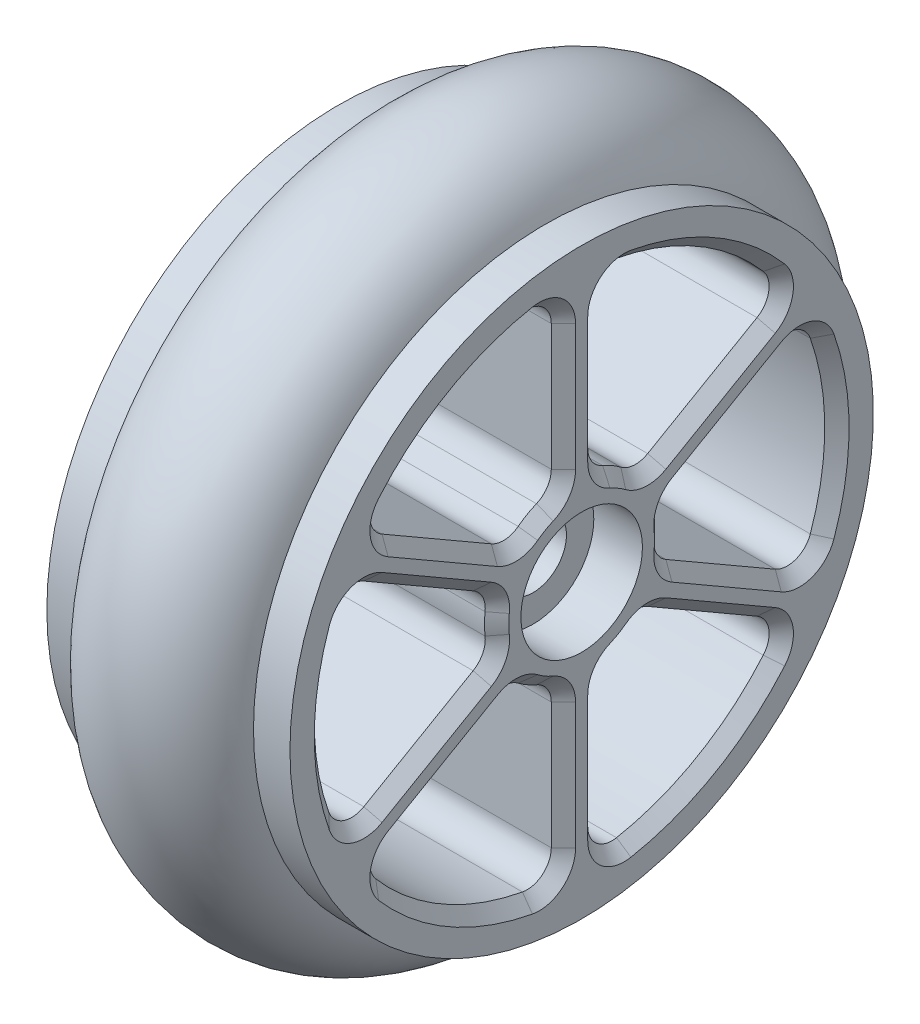
SolidWorks part; units mm, degrees
ref_plane "Front Plane" through (0, 0, 0) normal (0, 0, 1) x (1, 0, 0)
ref_plane "Top Plane" through (0, 0, 0) normal (0, 1, 0) x (1, 0, 0)
ref_plane "Right Plane" through (0, 0, 0) normal (1, 0, 0) x (0, 0, -1)
sketch "Sketch1" plane through (0, 0, 0) normal (0, 0, 1) x (1, 0, 0)
  line L14 (-10, 24) -> (-10, 0)
  line L15 (-10, 0) -> (10, 0)
  line L16 (-29.6857, 0) -> (25.2979, 0) construction
  line L17 (10, 0) -> (10, 24)
  line L18 (0, 29.9527) -> (0, -13.4426) construction
  line L19 (-10, 24) -> (-7, 24)
  line L20 (10, 24) -> (7, 24)
  arc A0 (7, 24) -> (-7, 24) centre (0, 21.6) ccw
  point P7 (0, 29)
  dimension "D2" = 14
  dimension "D1" = 20
  dimension "D3" = 48
  dimension "D4" = 58
revolve "Revolve1" add sketch "Sketch1" angle 360 about L16
sketch "Sketch2" plane through (10, 0, 0) normal (1, 0, 0) x (0, 0, -1)
  circle A0 centre (0, 0) radius 2.75
  dimension "D1" = 5.5
extrude "Cut-Extrude1" cut sketch "Sketch2" against normal up to next
sketch "Sketch3" plane through (-10, 0, 0) normal (-1, 0, 0) x (0, 0, 1)
  circle A0 centre (0, 0) radius 5
  dimension "D1" = 10
extrude "Cut-Extrude2" cut sketch "Sketch3" against normal blind 4
sketch "Sketch4" plane through (10, 0, 0) normal (1, 0, 0) x (0, 0, -1)
  circle A0 centre (0, 0) radius 5
  circle A1 centre (0, 0) radius 5 construction
extrude "Cut-Extrude3" cut sketch "Sketch4" against normal blind 4
sketch "Sketch5" plane through (10, 0, 0) normal (1, 0, 0) x (0, 0, -1)
  line L0 (-18.1865, 10.5) -> (18.1865, -10.5) construction
  line L1 (0, -21) -> (18.1865, -10.5)
  line L2 (18.1865, -10.5) -> (18.1865, 10.5)
  line L3 (18.1865, 10.5) -> (0, 21)
  line L4 (0, 21) -> (-18.1865, 10.5)
  line L5 (-18.1865, 10.5) -> (-18.1865, -10.5)
  line L6 (-18.1865, -10.5) -> (0, -21)
  line L7 (18.1865, 10.5) -> (-18.1865, -10.5) construction
  line L8 (0, 21) -> (0, -21) construction
  line L9 (-1.5, 21) -> (-1.5, -21)
  line L10 (17.4365, 11.799) -> (-18.9365, -9.201)
  line L11 (-18.9365, 9.201) -> (17.4365, -11.799)
  line L12 (1.5, 21) -> (1.5, -21)
  line L13 (18.9365, 9.201) -> (-17.4365, -11.799)
  line L14 (-17.4365, 11.799) -> (18.9365, -9.201)
  circle A0 centre (0, 0) radius 5 construction
  circle A1 centre (0, 0) radius 24 construction
  circle A3 centre (0, 0) radius 7
  circle A5 centre (0, 0) radius 21
  circle A6 centre (0, 0) radius 18.1865 construction
  dimension "D1" = 3
  dimension "D4" = 2
  dimension "D2" = 1.5
  dimension "D3" = 1.5
extrude "Cut-Extrude4" cut sketch "Sketch5" against normal up to next contours L14 L4 L9 | A3 L9 L4 L14 | L12 L3 L10 | A3 L10 L3 L12 | L2 L14 L13 | A3 L14 L2 L13 | L1 L12 L11 | A3 L12 L1 L11 | L6 L13 L9 | A3 L13 L6 L9 | L11 L10 L5 | A3 L11 L5 L10 region at (10, -11.8228, -6.8259) region at (10, -16.7554, -9.6737) region at (10, -16.7554, 9.6737) region at (10, -11.8228, 6.8259) region at (10, 0, -13.6518) region at (10, 0, -19.3474) region at (10, 0, 19.3474) region at (10, 0, 13.6518) region at (10, 11.8228, 6.8259) region at (10, 11.8228, -6.8259) region at (10, 16.7554, -9.6737) region at (10, 16.7554, 9.6737)
fillet "Fillet2" radius 2 24 edges at (0, 11.7722, -17.3901) (0, 4.7177, -5.1714) (0, 6.8374, -1.5) (0, 20.9464, -1.5) (0, 20.9464, 1.5) (0, 11.7722, 17.3901) (0, 4.7177, 5.1714) (0, 6.8374, 1.5) (0, 9.1741, 18.8901) (0, -9.1741, 18.8901) (0, -2.1197, 6.6714) (0, 2.1197, 6.6714) (0, -6.8374, 1.5) (0, -4.7177, 5.1714) (0, -11.7722, 17.3901) (0, -20.9464, 1.5) (0, -20.9464, -1.5) (0, -11.7722, -17.3901) (0, -4.7177, -5.1714) (0, -6.8374, -1.5) (0, -2.1197, -6.6714) (0, 2.1197, -6.6714) (0, 9.1741, -18.8901) (0, -9.1741, -18.8901)
chamfer "Chamfer1" distance 1 angle 45 48 edges at (10, 6.0622, 3.5) (10, 7.186, 1.8333) (10, 5.1807, 5.3066) (10, 13.4832, 1.5) (10, 8.0406, 10.9268) (10, 20.2138, 2.2227) (10, 12.0318, 16.3943) (10, 18.1865, 10.5) (10, 0, 7) (10, 2.0053, 7.1399) (10, -2.0053, 7.1399) (10, 5.4426, 12.4268) (10, -5.4426, 12.4268) (10, 8.182, 18.617) (10, -8.182, 18.617) (10, 0, 21) (10, -6.0622, 3.5) (10, -5.1807, 5.3066) (10, -7.186, 1.8333) (10, -8.0406, 10.9268) (10, -13.4832, 1.5) (10, -12.0318, 16.3943) (10, -20.2138, 2.2227) (10, -18.1865, 10.5) (10, -6.0622, -3.5) (10, -7.186, -1.8333) (10, -5.1807, -5.3066) (10, -13.4832, -1.5) (10, -8.0406, -10.9268) (10, -20.2138, -2.2227) (10, -12.0318, -16.3943) (10, -18.1865, -10.5) (10, 0, -7) (10, -2.0053, -7.1399) (10, 2.0053, -7.1399) (10, -5.4426, -12.4268) (10, 5.4426, -12.4268) (10, -8.182, -18.617) (10, 8.182, -18.617) (10, 0, -21) (10, 6.0622, -3.5) (10, 5.1807, -5.3066) (10, 7.186, -1.8333) (10, 8.0406, -10.9268) (10, 13.4832, -1.5) (10, 12.0318, -16.3943) (10, 20.2138, -2.2227) (10, 18.1865, -10.5)
sketch "Sketch8" plane through (0, 0, 0) normal (0, 0, 1) x (1, 0, 0)
  line L0 (-7, 24) -> (-7, -24) construction
  line L1 (7, 24) -> (7, -24) construction
  line L2 (-7, 24) -> (-7, -24)
  line L3 (7, 24) -> (7, -24)
  line L4 (-6, 23.8271) -> (-6, -23.8271)
  line L5 (6, 23.8271) -> (6, -23.8271)
  line L6 (-6, 22.8271) -> (6, 22.8271)
  line L7 (-25.0311, 0) -> (27.3418, 0) construction
  arc A0 (7, 24) -> (-7, 24) centre (0, 21.6) ccw construction
  arc A1 (7, 24) -> (-7, 24) centre (0, 21.6) ccw
  arc A2 (-7, -24) -> (7, -24) centre (0, -21.6) ccw construction
  arc A3 (-7, -24) -> (7, -24) centre (0, -21.6) ccw
  arc A4 (6, 23.8271) -> (-6, 23.8271) centre (0, 21.6) ccw
  arc A5 (-6, -23.8271) -> (6, -23.8271) centre (0, -21.6) ccw
  dimension "D2" = 1
  dimension "D1" = 1
revolve "Cut-Revolve1" cut sketch "Sketch8" angle 360 about L7 region at (0, 25.0021, 0)
ref_plane "Plane1" through (0, 0, 15) normal (0, 0, 1) x (1, 0, 0)
sketch "Sketch9" plane through (0, 0, 15) normal (0, 0, 1) x (1, 0, 0)
  circle A0 centre (0, 0) radius 1.5
  dimension "D1" = 3
extrude "Cut-Extrude6" cut sketch "Sketch9" along normal up to next
mirror "Mirror1" about plane through (0, 0, 0) normal (0, 0, 1) of "Cut-Extrude6"
sketch "Sketch7" [suppressed] plane through (4, 0, 0) normal (-1, 0, 0) x (0, 0, 1)
  circle A1 centre (0, 0) radius 5
  circle A2 centre (0, 0) radius 5
  dimension "D1" = 0
extrude "Cut-Extrude5" [suppressed] cut sketch "Sketch7" against normal blind 0.5
